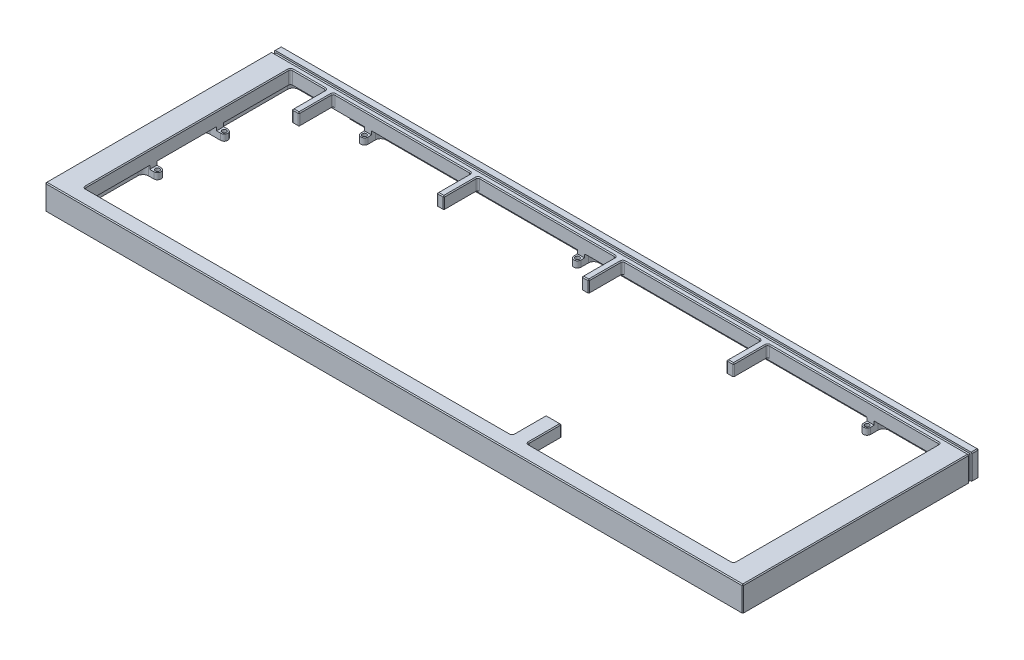
SolidWorks part; units mm, degrees
material "6061-T6 (SS)"
ref_plane "Front Plane" through (0, 0, 0) normal (0, 0, 1) x (1, 0, 0)
ref_plane "Top Plane" through (0, 0, 0) normal (0, 1, 0) x (1, 0, 0)
ref_plane "Right Plane" through (0, 0, 0) normal (1, 0, 0) x (0, 0, -1)
sketch "Sketch1" plane through (0, 0, 0) normal (0, 1, 0) x (1, 0, 0)
  line L1 (0, 0) -> (390, 0)
  line L2 (0, 0) -> (0, 132)
  line L3 (0, 132) -> (390, 132)
  line L4 (390, 0) -> (390, 132)
  dimension "D1" = 132
  dimension "D2" = 390
extrude "Boss-Extrude1" add sketch "Sketch1" along normal blind 14
sketch "Sketch2" plane through (0, 0, 0) normal (0, -1, 0) x (1, 0, 0)
  line L0 (390, -132) -> (0, -132) construction
  line L1 (388, -130) -> (2, -130)
  line L2 (388, -130) -> (388, -2)
  line L3 (388, -2) -> (2, -2)
  line L4 (2, -130) -> (2, -2)
  line L5 (390, 0) -> (390, -132) construction
  point P4 (195, -130)
  point P7 (195, -132)
  point P8 (388, -66)
  point P11 (390, -66)
  dimension "D1" = 2
  dimension "D2" = 2
extrude "Cut-Extrude1" cut sketch "Sketch2" against normal blind 1
sketch "Sketch3" plane through (0, 14, 0) normal (0, 1, 0) x (1, 0, 0)
  line L1 (13.55, 123.625) -> (376.45, 123.625)
  line L2 (13.55, 123.625) -> (13.55, 8.375)
  line L3 (13.55, 8.375) -> (376.45, 8.375)
  line L4 (376.45, 123.625) -> (376.45, 8.375)
  line L5 (0, 132) -> (0, 0) construction
  line L6 (390, 132) -> (0, 132) construction
  point P6 (13.55, 66)
  point P9 (0, 66)
  point P10 (195, 123.625)
  point P13 (195, 132)
  dimension "D1" = 8.375
  dimension "D2" = 13.55
extrude "Cut-Extrude2" cut sketch "Sketch3" against normal through all
sketch "Sketch4" plane through (0, 1, 0) normal (0, -1, 0) x (-1, 0, 0)
  line L0 (-388, 130) -> (-388, 2) construction
  line L1 (-380.15, 128.7375) -> (-9.85, 128.7375)
  line L2 (-380.15, 128.7375) -> (-380.15, 3.2625)
  line L3 (-380.15, 3.2625) -> (-9.85, 3.2625)
  line L4 (-9.85, 128.7375) -> (-9.85, 3.2625)
  line L6 (-13.55, 123.625) -> (-376.45, 123.625) construction
  line L7 (-379.15, 51.7125) -> (-379.15, 79.5255) construction
  line L9 (-333.1125, 124.7375) -> (-180.7125, 124.7375) construction
  point P4 (-380.15, 66)
  point P7 (-388, 66)
  point P12 (-195, 123.625)
  point P13 (-195, 128.7375)
  dimension "D1" = 1
  dimension "D2" = 4
extrude "Cut-Extrude3" cut sketch "Sketch4" against normal blind 5.5
sketch "Sketch5" plane through (0, 6.5, 0) normal (0, -1, 0) x (1, 0, 0)
  line L0 (13.55, -8.375) -> (376.45, -8.375) construction
  line L1 (380.15, -128.7375) -> (380.15, -3.2625) construction
  line L2 (374.15, -48.95) -> (380.15, -48.95)
  line L3 (374.15, -48.95) -> (374.15, -44.95)
  line L4 (374.15, -44.95) -> (380.15, -44.95)
  line L5 (380.15, -48.95) -> (380.15, -44.95)
  line L6 (380.15, -3.2625) -> (9.85, -3.2625) construction
  line L7 (301.775, -10.275) -> (297.775, -10.275)
  line L8 (301.775, -10.275) -> (301.775, -3.2625)
  line L9 (301.775, -3.2625) -> (297.775, -3.2625)
  line L10 (297.775, -10.275) -> (297.775, -3.2625)
  line L11 (9.85, -3.2625) -> (9.85, -128.7375) construction
  line L12 (87.4625, -10.275) -> (83.4625, -10.275)
  line L13 (87.4625, -10.275) -> (87.4625, -3.2625)
  line L14 (87.4625, -3.2625) -> (83.4625, -3.2625)
  line L15 (83.4625, -10.275) -> (83.4625, -3.2625)
  line L16 (15.85, -48.95) -> (9.85, -48.95)
  line L17 (15.85, -48.95) -> (15.85, -44.95)
  line L18 (15.85, -44.95) -> (9.85, -44.95)
  line L19 (9.85, -48.95) -> (9.85, -44.95)
  line L20 (9.85, -128.7375) -> (380.15, -128.7375) construction
  line L21 (15.85, -86.288) -> (9.85, -86.288)
  line L22 (15.85, -86.288) -> (15.85, -82.288)
  line L23 (15.85, -82.288) -> (9.85, -82.288)
  line L24 (9.85, -86.288) -> (9.85, -82.288)
  line L25 (58.8875, -121.625) -> (54.8875, -121.625)
  line L26 (58.8875, -121.625) -> (58.8875, -128.7375)
  line L27 (58.8875, -128.7375) -> (54.8875, -128.7375)
  line L28 (54.8875, -121.625) -> (54.8875, -128.7375)
  line L30 (177.95, -121.625) -> (173.95, -121.625)
  line L31 (177.95, -121.625) -> (177.95, -128.7375)
  line L32 (177.95, -128.7375) -> (173.95, -128.7375)
  line L33 (173.95, -121.625) -> (173.95, -128.7375)
  line L34 (339.875, -121.625) -> (335.875, -121.625)
  line L35 (339.875, -121.625) -> (339.875, -128.7375)
  line L36 (339.875, -128.7375) -> (335.875, -128.7375)
  line L37 (335.875, -121.625) -> (335.875, -128.7375)
  line L38 (374.15, -86.288) -> (380.15, -86.288)
  line L39 (374.15, -86.288) -> (374.15, -82.288)
  line L40 (374.15, -82.288) -> (380.15, -82.288)
  line L41 (380.15, -86.288) -> (380.15, -82.288)
  line L42 (380.15, -128.7375) -> (380.15, -3.2625) construction
  circle A0 centre (374.15, -46.95) radius 2
  circle A1 centre (374.15, -84.288) radius 2
  circle A2 centre (337.875, -121.625) radius 2
  circle A3 centre (299.775, -10.275) radius 2
  circle A4 centre (85.4625, -10.275) radius 2
  circle A5 centre (15.85, -46.95) radius 2
  circle A6 centre (175.95, -121.625) radius 2
  circle A7 centre (56.8875, -121.625) radius 2
  circle A8 centre (15.85, -84.288) radius 2
  arc A9 (374.15, -44.95) -> (374.15, -48.95) centre (374.15, -46.95) ccw construction
  arc A10 (374.15, -82.288) -> (374.15, -86.288) centre (374.15, -84.288) ccw construction
  arc A14 (339.875, -121.625) -> (335.875, -121.625) centre (337.875, -121.625) ccw construction
  arc A15 (177.95, -121.625) -> (173.95, -121.625) centre (175.95, -121.625) ccw construction
  arc A16 (297.3938, -11.2312) -> (302.1562, -11.2312) centre (299.775, -11.2312) ccw construction
  arc A17 (83.0812, -11.2312) -> (87.8437, -11.2312) centre (85.4625, -11.2312) ccw construction
  arc A20 (58.8875, -121.625) -> (54.8875, -121.625) centre (56.8875, -121.625) ccw construction
  arc A22 (15.85, -86.688) -> (15.85, -81.888) centre (15.85, -84.288) ccw construction
  arc A23 (15.85, -49.35) -> (15.85, -44.55) centre (15.85, -46.95) ccw construction
  point P47 (299.775, -13.6125)
  point P52 (85.4625, -13.6125)
  dimension "D2" = 4
  dimension "D1" = 1.9
extrude "Boss-Extrude2" add sketch "Sketch5" along normal up to surface (5.5 mm away) contours L40 L41 L38 L39 | A1 | L4 L5 L2 L3 | A0 | A3 | L8 L9 L10 L7 | L35 L36 L37 L34 | A2 | L33 L32 L31 L30 | A6 | L28 L27 L26 L25 | A7 | L16 L19 L18 L17 | A5 | A8 | L21 L24 L23 L22 | L15 L14 L13 L12 | A4 up to face at (195, 1, -66)
sketch "Sketch6" plane through (0, 6.5, 0) normal (0, 1, 0) x (1, 0, 0)
  line L1 (13.55, 123.625) -> (376.45, 123.625)
  line L2 (13.55, 123.625) -> (13.55, 8.375)
  line L3 (13.55, 8.375) -> (376.45, 8.375)
  line L4 (376.45, 123.625) -> (376.45, 8.375)
extrude "Cut-Extrude4" cut sketch "Sketch6" against normal blind 2
sketch "Sketch7" plane through (0, 1, 0) normal (0, -1, 0) x (-1, 0, 0)
  line L1 (-380.15, 82.288) -> (-383.15, 82.288)
  line L2 (-380.15, 82.288) -> (-380.15, 48.95)
  line L3 (-380.15, 48.95) -> (-383.15, 48.95)
  line L4 (-383.15, 82.288) -> (-383.15, 48.95)
  line L5 (-9.85, 82.288) -> (-6.85, 82.288)
  line L6 (-9.85, 82.288) -> (-9.85, 48.95)
  line L7 (-9.85, 48.95) -> (-6.85, 48.95)
  line L8 (-6.85, 82.288) -> (-6.85, 48.95)
  line L9 (-15.85, 48.95) -> (-9.85, 48.95) construction
  line L10 (-374.15, 48.95) -> (-380.15, 48.95) construction
  dimension "D1" = 3
extrude "Cut-Extrude5" cut sketch "Sketch7" against normal up to surface (5.5 mm away) up to face at (26.0958, 6.5, -112.8835)
sketch "Sketch8" plane through (0, 6.5, 0) normal (0, -1, 0) x (-1, 0, 0)
  point P0 (-359.7125, 126.5375)
  point P1 (-380.95, 65.619)
  point P3 (-340.6625, 5.4625)
  point P5 (-212.375, 5.4625)
  point P9 (-46.9563, 5.4625)
  point P11 (-9.05, 65.619)
  point P13 (-25.85, 126.5375)
  point P15 (-116.4187, 126.5375)
  point P19 (-256.9125, 126.5375)
hole_wizard "M2x0.4 Tapped Hole1" positions "3DSketch1" profile "Sketch9" tap size "M2x0.4" standard "ANSI Metric"
sketch3d "3DSketch1"
  point P0 (359.7125, 6.5, -126.5375)
  point P3 (380.95, 6.5, -65.619)
  point P6 (340.6625, 6.5, -5.4625)
  point P9 (212.375, 6.5, -5.4625)
  point P12 (256.9125, 6.5, -126.5375)
  point P21 (116.4187, 6.5, -126.5375)
  point P24 (25.85, 6.5, -126.5375)
  point P27 (9.05, 6.5, -65.619)
  point P30 (46.9563, 6.5, -5.4625)
sketch "Sketch9" plane through (359.7125, 6.5, -126.5375) normal (1, 0, 0) x (0, 0, -1)
  line L0 (0, 0) -> (0, 4.4807)
  line L1 (0, 4.4807) -> (0.8, 4)
  line L2 (0.8, 4) -> (0.8, 0)
  line L5 (0.8, 0) -> (0, 0)
  line L10 (0, 4.4807) -> (-0.8, 4) construction
  line L11 (0, -6.35) -> (0, 107.95) construction
  dimension "Tap Drill Dia." = 1.6
  dimension "Tap Drill Depth" = 4
  dimension "Drill Angle" = 118
cosmetic thread "Hole Thread1" parameters "D1"=4, "D2"=2
cosmetic thread "Hole Thread2" parameters "D1"=4, "D2"=2
cosmetic thread "Hole Thread3" parameters "D1"=4, "D2"=2
cosmetic thread "Hole Thread4" parameters "D1"=4, "D2"=2
cosmetic thread "Hole Thread7" parameters "D1"=4, "D2"=2
cosmetic thread "Hole Thread8" parameters "D1"=4, "D2"=2
cosmetic thread "Hole Thread9" parameters "D1"=4, "D2"=2
cosmetic thread "Hole Thread10" parameters "D1"=4, "D2"=2
cosmetic thread "Hole Thread11" parameters "D1"=4, "D2"=2
sketch "Sketch10" plane through (0, 0, -132) normal (0, 0, -1) x (-1, 0, 0)
  line L0 (-390, 0) -> (0, 0) construction
  line L1 (-41.7062, 0) -> (-29.2062, 0)
  line L2 (-41.7062, 0) -> (-41.7062, 1.3)
  line L3 (-41.7062, 1.3) -> (-29.2062, 1.3)
  line L4 (-29.2062, 0) -> (-29.2062, 1.3)
  line L5 (-32.3112, -2.985) -> (-38.6012, -2.985) construction
  point P6 (-35.4562, 0)
  point P9 (-35.4562, -2.985)
  dimension "D1" = 12.5
  dimension "D2" = 1.3
extrude "Cut-Extrude6" cut sketch "Sketch10" against normal blind 10
sketch "Sketch11" plane through (0, 1.3, 0) normal (0, -1, 0) x (1, 0, 0)
  line L0 (29.2062, -128.7375) -> (41.7062, -128.7375) construction
  line L1 (41.7062, -128.7375) -> (29.2062, -128.7375)
  line L2 (41.7062, -128.7375) -> (41.7062, -129.7375)
  line L3 (41.7062, -129.7375) -> (29.2062, -129.7375)
  line L4 (29.2062, -128.7375) -> (29.2062, -129.7375)
  line L5 (29.2062, -132) -> (41.7062, -132) construction
  point P6 (35.4562, -129.7375)
  point P9 (35.4562, -132)
  dimension "D1" = 12.5
  dimension "D2" = 1
extrude "Cut-Extrude7" cut sketch "Sketch11" against normal blind 2
sketch "Sketch12" plane through (0, 4.5, 0) normal (0, 1, 0) x (1, 0, 0)
  point P0 (15.85, 84.288)
  point P1 (15.85, 46.95)
  point P3 (85.4625, 10.275)
  point P5 (299.775, 10.275)
  point P7 (374.15, 46.95)
  point P9 (374.15, 84.288)
  point P11 (337.875, 121.625)
  point P13 (175.95, 121.625)
  point P15 (56.8875, 121.625)
hole_wizard "M2 Clearance Hole1" positions "3DSketch2" profile "Sketch13" hole size "M2" standard "ANSI Metric" end condition through all
sketch3d "3DSketch2"
  point P0 (15.85, 4.5, -46.95)
  point P3 (15.85, 4.5, -84.288)
  point P6 (56.8875, 4.5, -121.625)
  point P9 (85.4625, 4.5, -10.275)
  point P12 (175.95, 4.5, -121.625)
  point P15 (299.775, 4.5, -10.275)
  point P18 (374.15, 4.5, -46.95)
  point P21 (374.15, 4.5, -84.288)
  point P24 (337.875, 4.5, -121.625)
sketch "Sketch13" plane through (15.85, 4.5, -46.95) normal (1, 0, 0) x (0, 0, 1)
  line L0 (0, 0) -> (0, 4.5)
  line L1 (0, 4.5) -> (1.2, 4.5)
  line L2 (1.2, 4.5) -> (1.2, 0)
  line L5 (1.2, 0) -> (0, 0)
  line L11 (0, -6.35) -> (0, 107.95) construction
  dimension "Thru Hole Dia." = 2.4
  dimension "Thru Hole Depth" = 4.5
fillet "Fillet1" radius 3 24 edges at (380.15, 3.75, -3.2625) (9.85, 3.75, -3.2625) (29.2062, 2.3, -129.7375) (41.7062, 2.3, -129.7375) (177.95, 3.75, -128.7375) (173.95, 3.75, -128.7375) (54.8875, 3.75, -128.7375) (58.8875, 3.75, -128.7375) (9.85, 3.75, -128.7375) (9.85, 3.75, -86.288) (6.85, 3.75, -82.288) (6.85, 3.75, -48.95) (9.85, 3.75, -44.95) (87.4625, 3.75, -3.2625) (83.4625, 3.75, -3.2625) (297.775, 3.75, -3.2625) (301.775, 3.75, -3.2625) (380.15, 3.75, -44.95) (383.15, 3.75, -48.95) (380.15, 3.75, -86.288) (383.15, 3.75, -82.288) (380.15, 3.75, -128.7375) (335.875, 3.75, -128.7375) (339.875, 3.75, -128.7375)
fillet "Fillet2" radius 4 4 edges at (2, 0.5, -2) (2, 0.5, -130) (388, 0.5, -130) (388, 0.5, -2)
sketch "Sketch14" plane through (0, 14, 0) normal (0, 1, 0) x (1, 0, 0)
  line L0 (376.45, 123.625) -> (13.55, 123.625) construction
  line L1 (33.55, 123.625) -> (37.3625, 123.625)
  line L2 (33.55, 123.625) -> (33.55, 104.575)
  line L3 (33.55, 104.575) -> (37.3625, 104.575)
  line L4 (37.3625, 123.625) -> (37.3625, 104.575)
  line L5 (13.55, 8.375) -> (376.45, 8.375) construction
  line L6 (114.5125, 123.625) -> (118.325, 123.625)
  line L7 (114.5125, 123.625) -> (114.5125, 104.575)
  line L8 (114.5125, 104.575) -> (118.325, 104.575)
  line L9 (118.325, 123.625) -> (118.325, 104.575)
  line L14 (276.4375, 123.625) -> (280.25, 123.625)
  line L15 (276.4375, 123.625) -> (276.4375, 104.575)
  line L16 (276.4375, 104.575) -> (280.25, 104.575)
  line L17 (280.25, 123.625) -> (280.25, 104.575)
  line L18 (252.6438, 8.375) -> (261.2, 8.375)
  line L19 (252.6438, 8.375) -> (252.6438, 27.425)
  line L20 (252.6438, 27.425) -> (261.2, 27.425)
  line L21 (261.2, 8.375) -> (261.2, 27.425)
  line L22 (30.55, 120.125) -> (30.55, 107.125) construction
  line L23 (40.3625, 120.125) -> (40.3625, 107.125) construction
  line L24 (111.5125, 120.125) -> (111.5125, 107.125) construction
  line L25 (121.325, 120.125) -> (121.325, 107.125) construction
  line L26 (192.475, 120.125) -> (192.475, 107.125) construction
  line L27 (202.2875, 120.125) -> (202.2875, 107.125) construction
  line L28 (273.4375, 120.125) -> (273.4375, 107.125) construction
  line L29 (195.475, 123.625) -> (199.2875, 123.625)
  line L30 (195.475, 123.625) -> (195.475, 104.575)
  line L31 (195.475, 104.575) -> (199.2875, 104.575)
  line L32 (199.2875, 123.625) -> (199.2875, 104.575)
  line L33 (283.25, 120.125) -> (283.25, 107.125) construction
  line L34 (247.2437, 24.875) -> (247.2437, 11.875) construction
  line L35 (264.2, 24.875) -> (264.2, 11.875) construction
  line L36 (257.5562, 30.425) -> (270.5562, 30.425) construction
  line L37 (36.1, 101.575) -> (49.1, 101.575) construction
  dimension "D1" = 3
  dimension "D2" = 3
  dimension "D3" = 3
  dimension "D4" = 3
  dimension "D5" = 3
  dimension "D6" = 3
  dimension "D7" = 3
  dimension "D8" = 3
  dimension "D9" = 5.4
  dimension "D10" = 3
  dimension "D11" = 3
  dimension "D12" = 3
extrude "Boss-Extrude4" add sketch "Sketch14" against normal offset from surface (6.5 mm away) 1 up to face at (9.05, 6.5, -66.419)
fillet "Fillet3" radius 1 14 edges at (376.45, 10.25, -123.625) (376.45, 10.25, -8.375) (13.55, 10.25, -8.375) (13.55, 10.25, -123.625) (261.2, 10.75, -8.375) (252.6438, 10.75, -8.375) (276.4375, 10.75, -123.625) (280.25, 10.75, -123.625) (199.2875, 10.75, -123.625) (195.475, 10.75, -123.625) (118.325, 10.75, -123.625) (114.5125, 10.75, -123.625) (37.3625, 10.75, -123.625) (33.55, 10.75, -123.625)
fillet "Fillet4" radius 0.5 10 edges at (252.6438, 10.75, -27.425) (261.2, 10.75, -27.425) (276.4375, 10.75, -104.575) (280.25, 10.75, -104.575) (195.475, 10.75, -104.575) (199.2875, 10.75, -104.575) (114.5125, 10.75, -104.575) (118.325, 10.75, -104.575) (37.3625, 10.75, -104.575) (33.55, 10.75, -104.575)
sketch "Sketch15" plane through (0, 14, 0) normal (0, 1, 0) x (1, 0, 0)
  line L0 (0, 132) -> (0, 0) construction
  line L1 (0, 128.125) -> (390, 128.125)
  line L2 (0, 128.125) -> (0, 126.125)
  line L3 (0, 126.125) -> (390, 126.125)
  line L4 (390, 128.125) -> (390, 126.125)
  line L5 (390, 0) -> (390, 132) construction
  line L6 (32.55, 123.625) -> (14.55, 123.625) construction
  point P10 (0, 127.125)
  dimension "D1" = 3.5
  dimension "D2" = 2
extrude "Cut-Extrude8" cut sketch "Sketch15" against normal blind 1
sketch "Sketch16" plane through (0, 13, 0) normal (0, 1, 0) x (1, 0, 0)
  line L0 (0, 126.125) -> (390, 126.125) construction
  line L1 (0, 128.125) -> (1, 128.125)
  line L2 (0, 128.125) -> (0, 126.125)
  line L3 (0, 126.125) -> (1, 126.125)
  line L4 (1, 128.125) -> (1, 126.125)
  line L5 (390, 128.125) -> (0, 128.125) construction
  line L6 (389, 128.125) -> (390, 128.125)
  line L7 (389, 128.125) -> (389, 126.125)
  line L8 (389, 126.125) -> (390, 126.125)
  line L9 (390, 128.125) -> (390, 126.125)
  dimension "D1" = 1
extrude "Cut-Extrude9" cut sketch "Sketch16" against normal through all
chamfer "Chamfer1" distance 0.5 angle 45 63 edges at (114.6589, 14, -104.7214) (199.1411, 14, -104.7214) (195.6214, 14, -104.7214) (280.1036, 14, -104.7214) (276.5839, 14, -104.7214) (261.0536, 14, -27.2786) (252.7902, 14, -27.2786) (0, 14, -63.0625) (390, 14, -130.0625) (390, 14, -63.0625) (177.95, 6.5, -124.6813) (195, 14, -132) (0, 14, -130.0625) (256.9125, 6.5, -128.7375) (334.9963, 6.5, -127.8588) (178.8287, 6.5, -127.8588) (0, 7, -132) (390, 7, -132) (390, 7, 0) (0, 7, 0) (318.825, 14, -8.375) (133.0969, 14, -8.375) (261.2, 14, -18.15) (328.35, 14, -123.625) (237.8625, 14, -123.625) (156.9, 14, -123.625) (75.9375, 14, -123.625) (23.55, 14, -123.625) (276.4375, 14, -113.85) (195.475, 14, -113.85) (114.5125, 14, -113.85) (33.55, 14, -113.85) (376.45, 14, -66) (13.55, 14, -66) (261.4929, 14, -8.6679) (252.3509, 14, -8.6679) (276.1446, 14, -123.3321) (280.5429, 14, -123.3321) (199.5804, 14, -123.3321) (195.1821, 14, -123.3321) (118.6179, 14, -123.3321) (114.2196, 14, -123.3321) (37.6554, 14, -123.3321) (33.2571, 14, -123.3321) (376.1571, 14, -123.3321) (376.1571, 14, -8.6679) (13.8429, 14, -8.6679) (335.875, 6.5, -124.6813) (13.8429, 14, -123.3321) (195, 14, 0) (256.9219, 14, -27.425) (35.4562, 14, -104.575) (37.3625, 14, -113.85) (116.4187, 14, -104.575) (118.325, 14, -113.85) (197.3812, 14, -104.575) (199.2875, 14, -113.85) (278.3438, 14, -104.575) (280.25, 14, -113.85) (252.6438, 14, -18.15) (33.6964, 14, -104.7214) (37.2161, 14, -104.7214) (118.1786, 14, -104.7214)
chamfer "Chamfer2" distance 0.2 angle 45 11 edges at (390, 0, -129.8125) (389.75, 0, -131.75) (215.6031, 0, -132) (14.8531, 0, -132) (0.25, 0, -131.75) (0, 0, -129.8125) (390, 0, -63.3125) (389.75, 0, -0.25) (195, 0, 0) (0.25, 0, -0.25) (0, 0, -63.3125)
